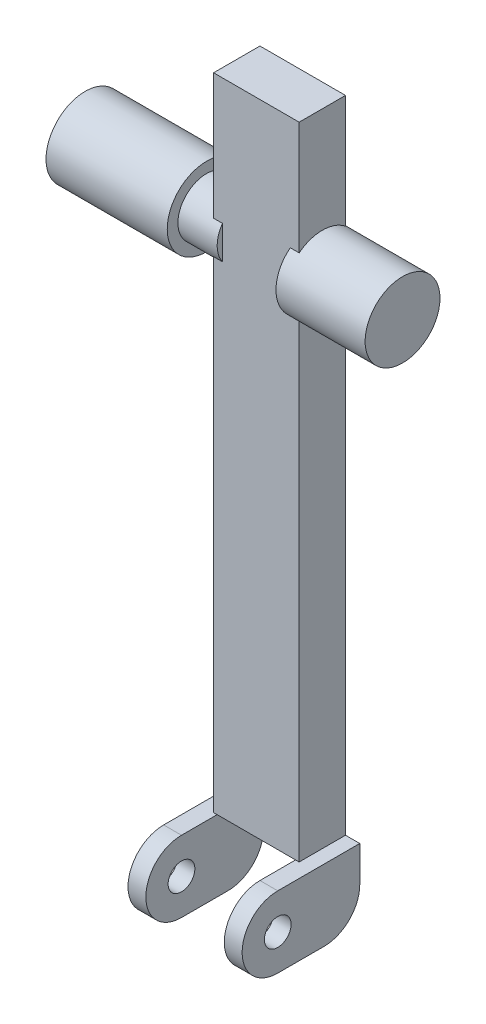
SolidWorks part; units mm, degrees
ref_plane "Front Plane" through (0, 0, 0) normal (0, 0, 1) x (1, 0, 0)
ref_plane "Top Plane" through (0, 0, 0) normal (0, 1, 0) x (1, 0, 0)
ref_plane "Right Plane" through (0, 0, 0) normal (1, 0, 0) x (0, 0, -1)
sketch "Sketch1" plane through (0, 0, 0) normal (0, 1, 0) x (1, 0, 0)
  line L1 (-24, 13) -> (24, 13)
  line L2 (-24, 13) -> (-24, -13)
  line L3 (-24, -13) -> (24, -13)
  line L4 (24, 13) -> (24, -13)
  line L5 (-24, 13) -> (24, -13) construction
  line L6 (-24, -13) -> (24, 13) construction
  point P0 (0, 0)
ref_plane "Plane1" through (19, 0, 0) normal (1, 0, 0) x (0, 0, -1)
sketch "Sketch2" plane through (19, 0, 0) normal (1, 0, 0) x (0, 0, -1)
  line L0 (13, 0) -> (-13, 0) construction
  circle A0 centre (0, 0) radius 21
ref_plane "Plane2" through (-19, 0, 0) normal (1, 0, 0) x (0, 0, -1)
sketch "Sketch3" plane through (-19, 0, 0) normal (1, 0, 0) x (0, 0, -1)
  line L0 (13, 0) -> (-13, 0) construction
  circle A0 centre (0, 0) radius 16
extrude "Boss-Extrude1" add sketch "Sketch3" against normal blind 22
ref_plane "Plane3" through (-41, 0, 0) normal (-1, 0, 0) x (0, 0, 1)
sketch "Sketch4" plane through (-41, 0, 0) normal (-1, 0, 0) x (0, 0, 1)
  circle A0 centre (0, 0) radius 22
extrude "Boss-Extrude2" add sketch "Sketch4" along normal blind 68
extrude "Boss-Extrude3" add sketch "Sketch2" along normal blind 50 separate body
extrude "Boss-Extrude5" add sketch "Sketch1" along normal blind 80 and the other way blind 279.4
ref_plane "Plane4" through (24, 0, 0) normal (1, 0, 0) x (0, 0, -1)
sketch "Sketch5" plane through (24, 0, 0) normal (1, 0, 0) x (0, 0, -1)
  line L1 (13, -279.4) -> (-33, -279.4)
  line L3 (13, -279.4) -> (13, -299.4)
  line L4 (-7, -319.4) -> (-33, -319.4)
  arc A0 (-33, -279.4) -> (-33, -319.4) centre (-33, -299.4) ccw
  arc A1 (-7, -319.4) -> (13, -299.4) centre (-7, -299.4) ccw
  dimension "D1" = 20
  dimension "D2" = 20
extrude "Boss-Extrude7" add sketch "Sketch5" along normal blind 8 and the other way blind 2 separate body
ref_plane "Plane8" through (22, 0, 0) normal (-1, 0, 0) x (0, 0, 1)
sketch "Sketch10" plane through (22, 0, 0) normal (-1, 0, 0) x (0, 0, 1)
  circle A0 centre (33, -299.4) radius 7.5
extrude "Cut-Extrude4" cut sketch "Sketch10" against normal up to vertex (10 mm away) up to point (32, -319.4, 33)
mirror "Mirror26" about plane through (0, 0, 0) normal (1, 0, 0) of "Cut-Extrude4", "Boss-Extrude7"
ref_point "Point1"
ref_point "Point2"
ref_axis "Axis1" through (69, 0, 0) along (-1, 0, 0)
sketch "Sketch11" plane through (-109, 0, 0) normal (-1, 0, 0) x (0, 0, 1)
  line L0 (0, 0) -> (0, 22) construction
  circle A0 centre (0, 0) radius 22 construction
ref_plane "Plane5" through (0, 0, 0) normal (1, 0, 0) x (0, 0, -1)
